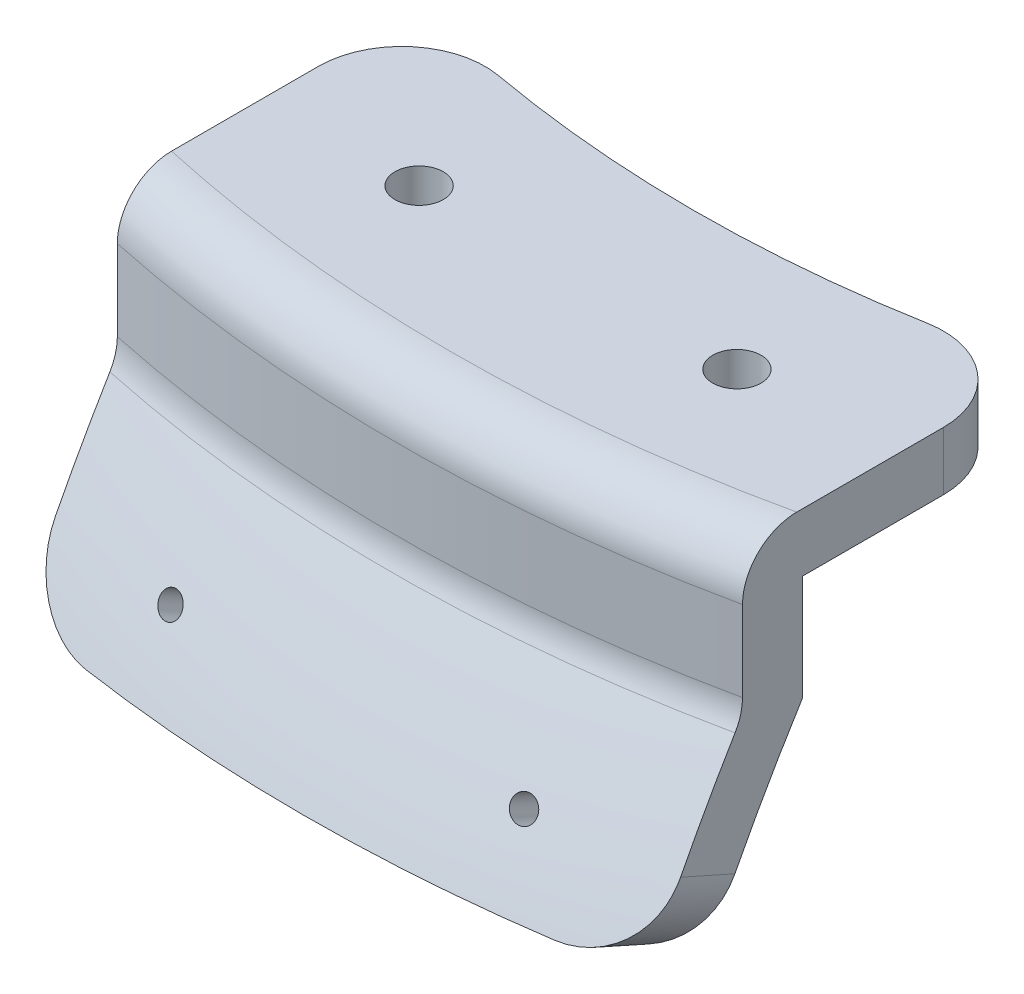
SolidWorks part; units mm, degrees
material "Polyether Polyol"
ref_plane "Front Plane" through (0, 0, 0) normal (0, 0, 1) x (1, 0, 0)
ref_plane "Top Plane" through (0, 0, 0) normal (0, 1, 0) x (1, 0, 0)
ref_plane "Right Plane" through (0, 0, 0) normal (1, 0, 0) x (0, 0, -1)
sketch "Sketch2" plane through (0, 0, 0) normal (1, 0, 0) x (0, 0, -1)
  line L0 (-173.3622, 191.5688) -> (-173.3622, 178.8688) construction
  line L1 (-191.634, 159.2436) -> (-185.2523, 156.3672) construction
  line L2 (-180.3622, 198.5688) -> (-180.3622, 180.8213) construction
  line L3 (-180.3622, 198.5688) -> (-144.7872, 198.5688) construction
  line L4 (-144.7872, 198.5688) -> (-144.7872, 191.5688) construction
  line L5 (-144.7872, 191.5688) -> (-173.3622, 191.5688) construction
  line L12 (0, 72.8698) -> (0, 191.5688) construction
  line L13 (-173.3622, 191.5688) -> (-173.3622, 178.8688)
  line L14 (-191.634, 159.2436) -> (-185.2523, 156.3672)
  line L15 (-180.3622, 198.5688) -> (-180.3622, 180.8213)
  line L16 (-180.3622, 198.5688) -> (-144.7872, 198.5688)
  line L17 (-144.7872, 198.5688) -> (-144.7872, 191.5688)
  line L18 (-144.7872, 191.5688) -> (-173.3622, 191.5688)
  arc A0 (-173.3622, 178.8688) -> (-185.2523, 156.3672) centre (0, 72.8698) ccw construction
  arc A1 (-180.3622, 180.8213) -> (-191.634, 159.2436) centre (0, 72.8698) ccw construction
  arc A4 (-173.3622, 178.8688) -> (-185.2523, 156.3672) centre (0, 72.8698) ccw
  arc A5 (-180.3622, 180.8213) -> (-191.634, 159.2436) centre (0, 72.8698) ccw
revolve "Revolve1" add sketch "Sketch2" angle 30 mid plane about L12
fillet "Fillet1" radius 6.35 2 edges at (0, 180.8213, 180.3622) (0, 198.5688, 180.3622)
sketch "Sketch3" plane through (0, 198.5688, 0) normal (0, -1, 0) x (1, 0, 0)
  circle A2 centre (-19.05, 158.6742) radius 3.5719 construction
  circle A3 centre (19.05, 158.6742) radius 3.5719 construction
  circle A4 centre (19.05, 158.6742) radius 2.9
  circle A5 centre (-19.05, 158.6742) radius 2.9
  dimension "D1" = 5.8
extrude "Cut-Extrude1" cut sketch "Sketch3" along normal through all contours A4 | A5 region at (19.05, 198.5688, 158.6742) region at (-19.05, 198.5688, 158.6742)
sketch "Sketch4" plane through (0, 198.5688, 0) normal (0, 1, 0) x (1, 0, 0)
  line L0 (37.4737, -139.8537) -> (45.0377, -168.0828) construction
  line L1 (37.4737, -139.8537) -> (-37.4737, -139.8537)
  line L2 (37.4737, -139.8537) -> (37.4737, -191.634)
  line L3 (37.4737, -191.634) -> (-37.4737, -191.634)
  line L4 (-37.4737, -139.8537) -> (-37.4737, -191.634)
  line L5 (-37.4737, -139.8537) -> (-45.0377, -168.0828) construction
  arc A0 (-37.4737, -139.8537) -> (37.4737, -139.8537) centre (0, 0) ccw construction
  arc A1 (-49.5985, -185.1043) -> (49.5985, -185.1043) centre (0, 0) ccw construction
extrude "Cut-Extrude2" cut sketch "Sketch4" against normal through all flip side to cut
fillet "Fillet2" radius 10 4 edges at (-37.4737, 195.0688, 139.8537) (37.4737, 195.0688, 139.8537)
sketch "Sketch5" plane through (0, 0, 0) normal (-1, 0, 0) x (0, 0, 1)
  line L0 (0, 72.8698) -> (181.0525, 165.1206) construction
  line L2 (0, -200000) -> (0, 218797.9879) construction
  arc A0 (185.2523, 156.3672) -> (173.3622, 178.8688) centre (0, 72.8698) ccw construction
  dimension "D1" = 63
ref_plane "Plane1" through (0, 57.8508, -29.4764) normal (0, 0.891, -0.454) x (0, 0.454, 0.891)
sketch "Sketch6" plane through (0, 57.8508, -29.4764) normal (0, 0.891, -0.454) x (0, 0.454, 0.891)
  line L0 (209.1764, 18.3006) -> (275.7942, 24.1289) construction
  line L2 (209.1764, 18.3006) -> (275.7942, 24.1289)
  line L3 (209.1764, 18.3006) -> (209.0457, 19.7949)
  line L4 (275.7942, 24.1289) -> (275.6635, 25.6232)
  line L5 (209.0457, 19.7949) -> (275.6635, 25.6232)
  line L6 (33.0822, 0) -> (236.2822, 0) construction
  ellipse E0 centre (81.2048, 0) end of major axis (81.2048, 144.7872) minor radius 129.0063 construction
  dimension "D1" = 5
  dimension "D2" = 1.5
revolve "Cut-Revolve1" cut sketch "Sketch6" angle 360 about L0
mirror "Mirror1" about plane through (0, 0, 0) normal (1, 0, 0) of "Cut-Revolve1"
